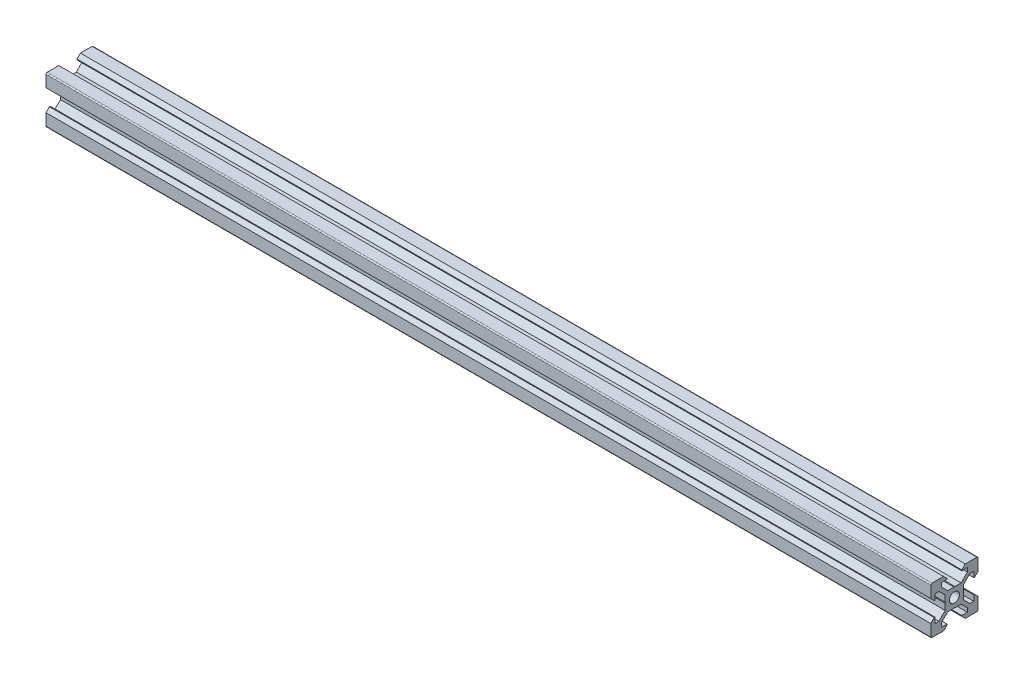
SolidWorks part; units mm, degrees
material "6061-T6 (SS)"
ref_plane "Top" through (0, 0, 0) normal (0, 0, 1) x (1, 0, 0)
ref_plane "Front" through (0, 0, 0) normal (0, 1, 0) x (1, 0, 0)
ref_plane "Right" through (0, 0, 0) normal (1, 0, 0) x (0, 0, -1)
sketch "Profile Sketch" plane through (0, 0, 0) normal (1, 0, 0) x (0, 0, -1)
  line L0 (-0.5, 10) -> (-5.42, 10)
  line L1 (-4.5, 8.2) -> (-4.5, 6.56)
  line L2 (-4.5, 6.56) -> (-7.16, 3.9)
  line L3 (-7.16, 3.9) -> (-9.79, 3.9)
  line L4 (-9.79, 3.9) -> (-10, 3.69)
  line L7 (-3.4387, 5.5) -> (-6.1, 2.8387)
  line L8 (-6.1, 2.8387) -> (-6.1, -0.21)
  line L9 (-6.875, 8.545) -> (-6.875, 8.2)
  line L10 (-6.875, 8.2) -> (-4.5, 8.2)
  line L11 (-6.875, 8.545) -> (-5.42, 10)
  line L12 (0, -10) -> (0, 10) construction
  line L13 (-20, 0) -> (20, 0) construction
  line L14 (-10, -10) -> (-10, 10) construction
  line L15 (-6.875, -8.545) -> (-5.42, -10)
  line L16 (-6.875, -8.2) -> (-4.5, -8.2)
  line L17 (-6.875, -8.545) -> (-6.875, -8.2)
  line L18 (-3.44, -5.5) -> (-6.1, -2.8387)
  line L21 (-7.16, -3.9) -> (-9.79, -3.9)
  line L22 (-4.5, -6.56) -> (-7.16, -3.9)
  line L23 (-4.5, -8.2) -> (-4.5, -6.56)
  line L24 (-0.5, -10) -> (-5.42, -10)
  line L25 (-10, 0) -> (-20, 10) construction
  line L26 (-18.545, 3.125) -> (-18.2, 3.125)
  line L27 (-13.125, -8.545) -> (-13.125, -8.2)
  line L28 (-13.125, -8.2) -> (-15.5, -8.2)
  line L29 (-13.125, -8.545) -> (-14.58, -10)
  line L30 (-15.5, -8.2) -> (-15.5, -6.56)
  line L31 (-15.5, -6.56) -> (-12.84, -3.9)
  line L32 (-12.84, -3.9) -> (-10.21, -3.9)
  line L33 (-20, 4.58) -> (-20, 9.5)
  line L34 (-13.9, 2.8387) -> (-13.9, 0.21)
  line L35 (-16.56, 5.5) -> (-13.9, 2.8387)
  line L36 (-12.84, 3.9) -> (-10.21, 3.9)
  line L37 (-15.5, 6.56) -> (-12.84, 3.9)
  line L38 (-15.5, 8.2) -> (-15.5, 6.56)
  line L39 (-13.125, 8.545) -> (-14.58, 10)
  line L40 (-13.125, 8.2) -> (-15.5, 8.2)
  line L41 (-13.125, 8.545) -> (-13.125, 8.2)
  line L42 (-18.2, 3.125) -> (-18.2, 5.5)
  line L43 (-18.545, 3.125) -> (-20, 4.58)
  line L44 (-18.2, 5.5) -> (-16.56, 5.5)
  line L45 (-14.58, 10) -> (-19.5, 10)
  line L46 (-16.56, -5.5) -> (-13.9, -2.8387)
  line L47 (-14.58, -10) -> (-19.5, -10)
  line L48 (-18.2, -5.5) -> (-16.56, -5.5)
  line L49 (-18.545, -3.125) -> (-20, -4.58)
  line L50 (-18.2, -3.125) -> (-18.2, -5.5)
  line L51 (-20, -4.58) -> (-20, -9.5)
  line L52 (-18.545, -3.125) -> (-18.2, -3.125)
  line L53 (10, -10) -> (10, 10) construction
  line L99 (-10, 3.69) -> (-10.21, 3.9)
  line L100 (-10, -3.69) -> (-10.21, -3.9)
  line L101 (-9.79, -3.9) -> (-10, -3.69)
  line L102 (-13.9, -0.21) -> (-13.69, 0)
  line L103 (-13.69, 0) -> (-13.9, 0.21)
  line L104 (-13.9, -0.21) -> (-13.9, -2.8387)
  line L105 (-6.1, -0.21) -> (-6.31, 0)
  line L106 (-6.31, 0) -> (-6.1, -0.21)
  line L107 (-6.1, -0.21) -> (-6.1, -2.8387)
  line L117 (-5.42, -10) -> (-0.5, -10)
  line L118 (20, -10) -> (20, 10) construction
  line L119 (20, -10) -> (-20, -10) construction
  line L120 (-20, -10) -> (-20, 10) construction
  line L121 (20, 10) -> (-20, 10) construction
  line L122 (20, -10) -> (-20, 10) construction
  line L123 (-20, -10) -> (20, 10) construction
  line L124 (-5.42, 10) -> (-0.5, 10)
  line L125 (-1.455, 3.125) -> (-1.8, 3.125)
  line L126 (-1.455, -3.125) -> (-1.8, -3.125)
  line L127 (-1.8, -5.5) -> (-3.44, -5.5)
  line L128 (-1.8, 5.5) -> (-3.44, 5.5)
  line L129 (-1.8, 3.125) -> (-1.8, 5.5)
  line L130 (-1.8, -3.125) -> (-1.8, -5.5)
  line L131 (0, -4.58) -> (0, -9.5)
  line L132 (0, 4.58) -> (0, 9.5)
  line L133 (-1.455, 3.125) -> (0, 4.58)
  line L134 (-1.455, -3.125) -> (0, -4.58)
  circle A0 centre (-10, 0) radius 2.1
  arc A1 (-19.5, 10) -> (-20, 9.5) centre (-19.5, 9.5) ccw
  arc A2 (-19.5, -10) -> (-20, -9.5) centre (-19.5, -9.5) cw
  arc A3 (-0.5, -10) -> (0, -9.5) centre (-0.5, -9.5) ccw
  arc A4 (-0.5, 10) -> (0, 9.5) centre (-0.5, 9.5) cw
  point P2 (-17.38, 5.5)
  point P35 (-2.4957, 0)
  point P76 (-2.62, 5.5)
  point P108 (0, -8.2)
  point P119 (0, 8.2)
  point P131 (0, 0)
  point P143 (0, 0)
  dimension "D4" = 5.42
  dimension "D5" = 40
  dimension "D6" = 4.2
  dimension "D16" = 0.5
  dimension "D1" = 0.21
  dimension "D2" = 45
  dimension "D3" = 20
  dimension "D7" = 1.5
  dimension "D8" = 1.8
  dimension "D9" = 10
  dimension "D10" = 3.9
  dimension "D11" = 3.9
  dimension "D13" = 3.125
  dimension "D14" = 5.5
  dimension "D15" = 1.64
extrude "Profile Extrude" add sketch "Profile Sketch" along normal blind 375 contours L126 L0 L11 L9 L10 L1 L2 L3 L4 L99 L36 L37 L38 L40 L41 L39 L45 A1 L33 L43 L26 L42 L44 L35 L34 L103 L102 L104 L46 L48 L50 L52 L49 L51 A2 L47 region at (0, 9.6536, 0.3464)
equation "\"M8x1.25_Close_Hole\"= 8.4"
